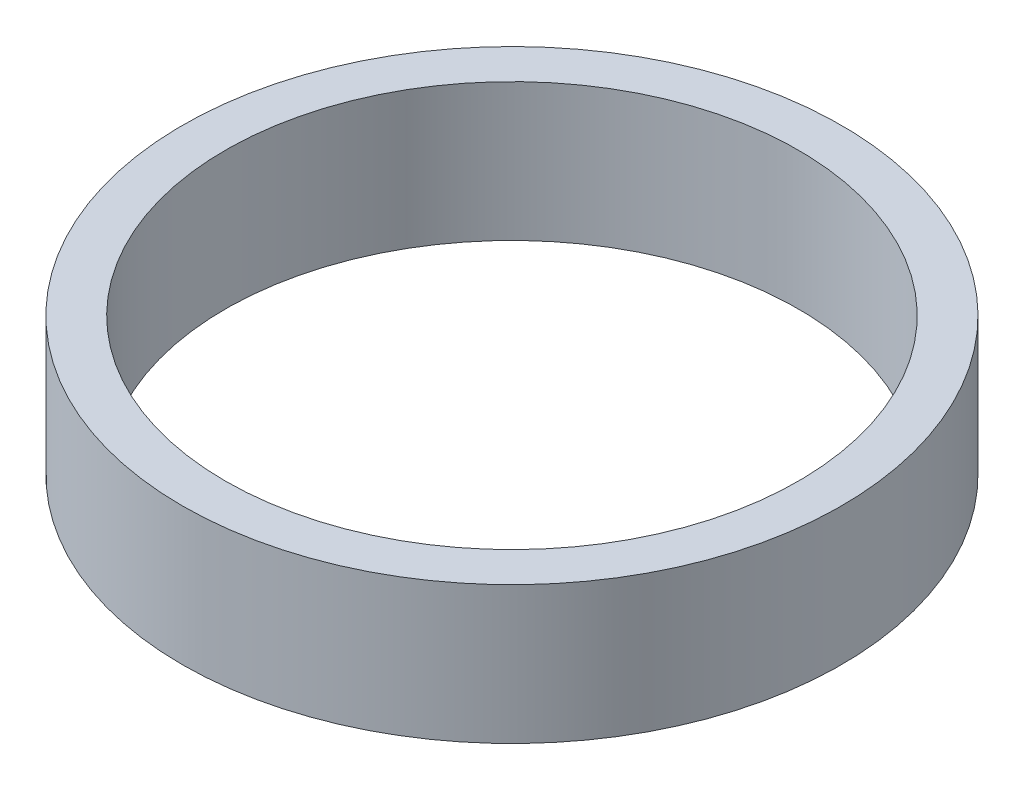
SolidWorks part; units mm, degrees
ref_plane "Front Plane" through (0, 0, 0) normal (0, 0, 1) x (1, 0, 0)
ref_plane "Top Plane" through (0, 0, 0) normal (0, 1, 0) x (1, 0, 0)
ref_plane "Right Plane" through (0, 0, 0) normal (1, 0, 0) x (0, 0, -1)
sketch "Sketch1" plane through (0, 0, 0) normal (0, 1, 0) x (1, 0, 0)
  circle A0 centre (0, 0) radius 57.5
  dimension "FLANGE_OD" = 115
extrude "Boss-Extrude1" add sketch "Sketch1" along normal blind 24
sketch "Sketch2" plane through (0, 0, 0) normal (0, 1, 0) x (1, 0, 0)
  circle A0 centre (0, 0) radius 50
  dimension "BORE_D" = 100
extrude "Cut-Extrude1" cut sketch "Sketch2" along normal through all
sketch "Sketch3" plane through (0, 24, 0) normal (0, 1, 0) x (1, 0, 0)
  circle A0 centre (0, 0) radius 26.7464 construction
  circle A1 centre (-26.7464, 0) radius 1.5
  dimension "BOLT_D" = 3
  dimension "BOLT_PCD" = 53.4929
extrude "Cut-Extrude2" cut sketch "Sketch3" against normal blind 17.1318 rebuild error yes
pattern_circular "CirPattern1" count 3 over 360 rebuild error yes
